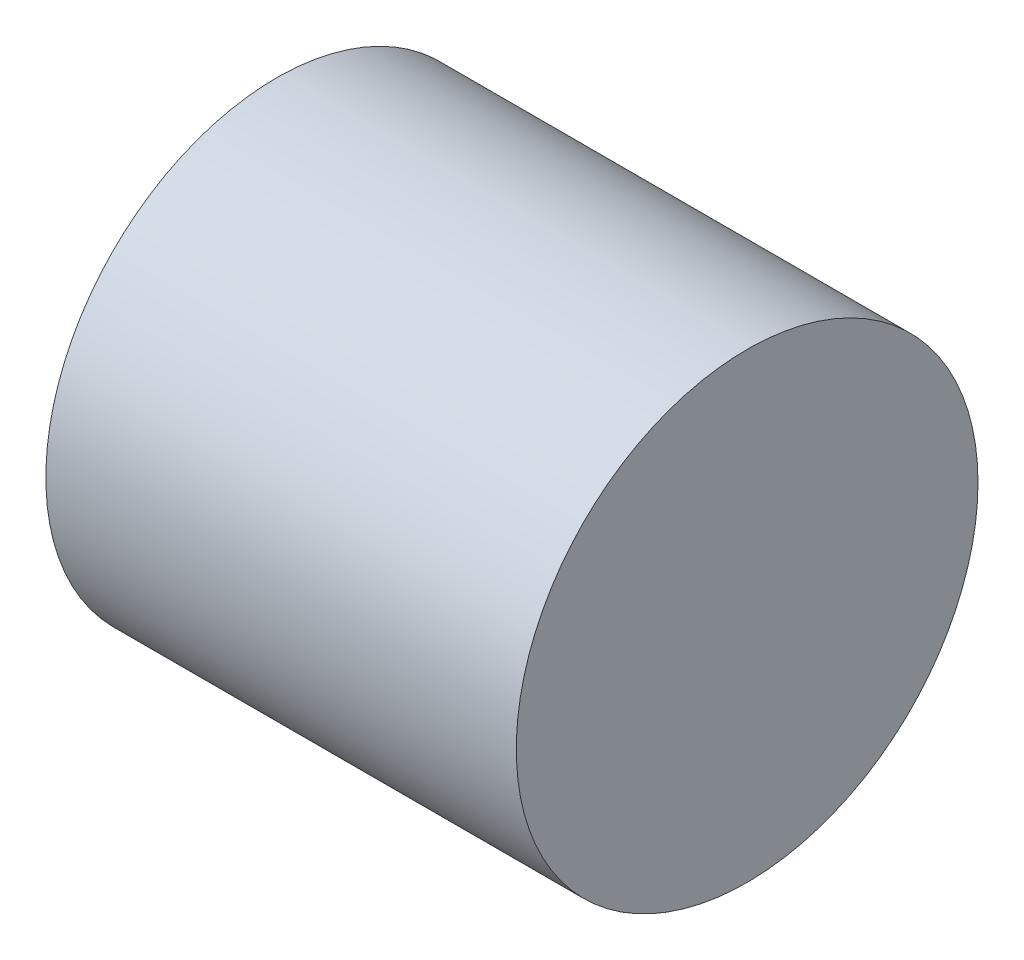
SolidWorks part; units mm, degrees
ref_plane "Plan de face" through (0, 0, 0) normal (0, 0, 1) x (1, 0, 0)
ref_plane "Plan de dessus" through (0, 0, 0) normal (0, 1, 0) x (1, 0, 0)
ref_plane "Plan de droite" through (0, 0, 0) normal (1, 0, 0) x (0, 0, -1)
sketch "Esquisse1" plane through (0, 0, 0) normal (1, 0, 0) x (0, 0, -1)
  circle A0 centre (0, 0) radius 73.61
  dimension "D1" = 147.22
extrude "Boss.-Extru.1" add sketch "Esquisse1" along normal blind 150 contours A0
